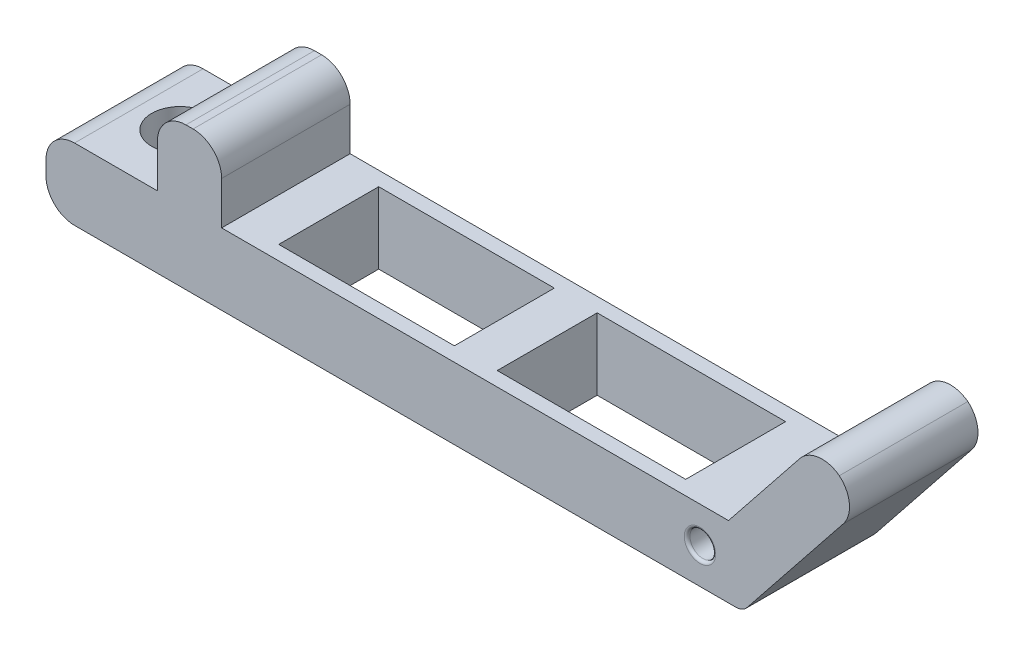
SolidWorks part; units mm, degrees
ref_plane "Front Plane" through (0, 0, 0) normal (0, 0, 1) x (1, 0, 0)
ref_plane "Top Plane" through (0, 0, 0) normal (0, 1, 0) x (1, 0, 0)
ref_plane "Right Plane" through (0, 0, 0) normal (1, 0, 0) x (0, 0, -1)
sketch "Szkic1" plane through (0, 0, 0) normal (0, 0, 1) x (1, 0, 0)
  line L6 (-27646.5587, -28.9023) -> (-27646.5587, -33.9023)
  line L7 (-27646.5587, -33.9023) -> (-27597.7587, -33.9023)
  line L8 (-27597.7587, -33.9023) -> (-27589.4735, -23.5176)
  line L9 (-27589.4735, -23.5176) -> (-27592.5221, -21.0854)
  line L10 (-27592.5221, -21.0854) -> (-27598.7587, -28.9023)
  line L11 (-27598.7587, -28.9023) -> (-27634.2587, -28.9023)
  line L12 (-27638.7587, -28.9023) -> (-27638.7587, -23.9023)
  line L13 (-27638.7587, -23.9023) -> (-27634.2587, -23.9023)
  line L14 (-27634.2587, -23.9023) -> (-27634.2587, -28.9023)
  line L15 (-27638.7587, -28.9023) -> (-27646.5587, -28.9023)
  line L16 (-27600.7587, -28.9023) -> (-27600.7587, -33.9023) construction
  circle A0 centre (-27600.7587, -31.4023) radius 0.9
  point P12 (-27600.7587, -31.4023)
  dimension "D9" = 1.8
  dimension "D1" = 3.9
  dimension "D2" = 47.8
  dimension "D3" = 10
  dimension "D4" = 5
  dimension "D5" = 48.8
  dimension "D6" = 4.5
  dimension "D7" = 5
  dimension "D8" = 7.8
  dimension "D10" = 2
extrude "Dodanie-wyciągnięcie1" add sketch "Szkic1" along normal blind 9
fillet "Zaokrąglenie1" radius 2 4 edges at (-27646.5587, -33.9023, 4.5) (-27634.2587, -23.9023, 4.5) (-27638.7587, -23.9023, 4.5) (-27646.5587, -28.9023, 4.5)
fillet "Zaokrąglenie3" radius 1 1 edges at (-27597.7587, -33.9023, 4.5)
ref_plane "Płaszczyzna1" through (0, -28.9023, 0) normal (0, 1, 0) x (1, 0, 0)
sketch "Szkic2" plane through (0, -28.9023, 0) normal (0, 1, 0) x (1, 0, 0)
  line L0 (-27641.6587, 0) -> (-27641.6587, -9) construction
  line L1 (-27638.7587, 0) -> (-27644.5587, 0) construction
  line L2 (-27638.7587, -9) -> (-27644.5587, -9) construction
  circle A0 centre (-27641.6587, -4.5) radius 2
  point P6 (-27641.6587, -4.5)
  dimension "D1" = 4
extrude "Wytnij-wyciągnięcie1" cut sketch "Szkic2" against normal through all
ref_plane "Płaszczyzna2" through (0, -28.9023, 0) normal (0, 1, 0) x (1, 0, 0)
sketch "Szkic3" plane through (0, -28.9023, 0) normal (0, 1, 0) x (1, 0, 0)
  line L0 (-27634.2587, -4.5) -> (-27598.7587, -4.5) construction
  line L1 (-27634.2587, -9) -> (-27634.2587, 0) construction
  line L2 (-27598.7587, -9) -> (-27598.7587, 0) construction
  line L3 (-27598.7587, -9) -> (-27634.2587, -9) construction
  line L4 (-27602.7587, -8) -> (-27615.9572, -8)
  line L5 (-27602.7587, -8) -> (-27602.7587, -1)
  line L6 (-27602.7587, -1) -> (-27615.9572, -1)
  line L7 (-27615.9572, -8) -> (-27615.9572, -1)
  line L8 (-27602.7587, -8) -> (-27615.9572, -1) construction
  line L9 (-27602.7587, -1) -> (-27615.9572, -8) construction
  line L10 (-27631.2587, -1) -> (-27618.9572, -1)
  line L11 (-27631.2587, -1) -> (-27631.2587, -8)
  line L12 (-27631.2587, -8) -> (-27618.9572, -8)
  line L13 (-27618.9572, -1) -> (-27618.9572, -8)
  line L14 (-27631.2587, -1) -> (-27618.9572, -8) construction
  line L15 (-27631.2587, -8) -> (-27618.9572, -1) construction
  point P6 (-27609.358, -4.5)
  point P11 (-27625.108, -4.5)
  dimension "D1" = 3
  dimension "D2" = 4
  dimension "D3" = 3
  dimension "D4" = 1
extrude "Wytnij-wyciągnięcie2" cut sketch "Szkic3" against normal through all
fillet "Zaokrąglenie4" radius 2 2 edges at (-27589.4735, -23.5176, 4.5) (-27592.5221, -21.0854, 4.5)
fillet "Zaokrąglenie5" radius 1 1 edges at (-27643.6587, -33.9023, 4.5)
ref_axis "Oś1" through (-27641.6587, -33.0151, 4.5) along (0, 1, 0)
ref_point "Punkt2"
fillet "Zaokrąglenie7" radius 0.2 2 edges at (-27599.8587, -31.4023, 9) (-27599.8587, -31.4023, 0)
ref_plane "Płaszczyzna Dolnia" through (0, -33.9023, 0) normal (0, -1, 0) x (-1, 0, 0)
